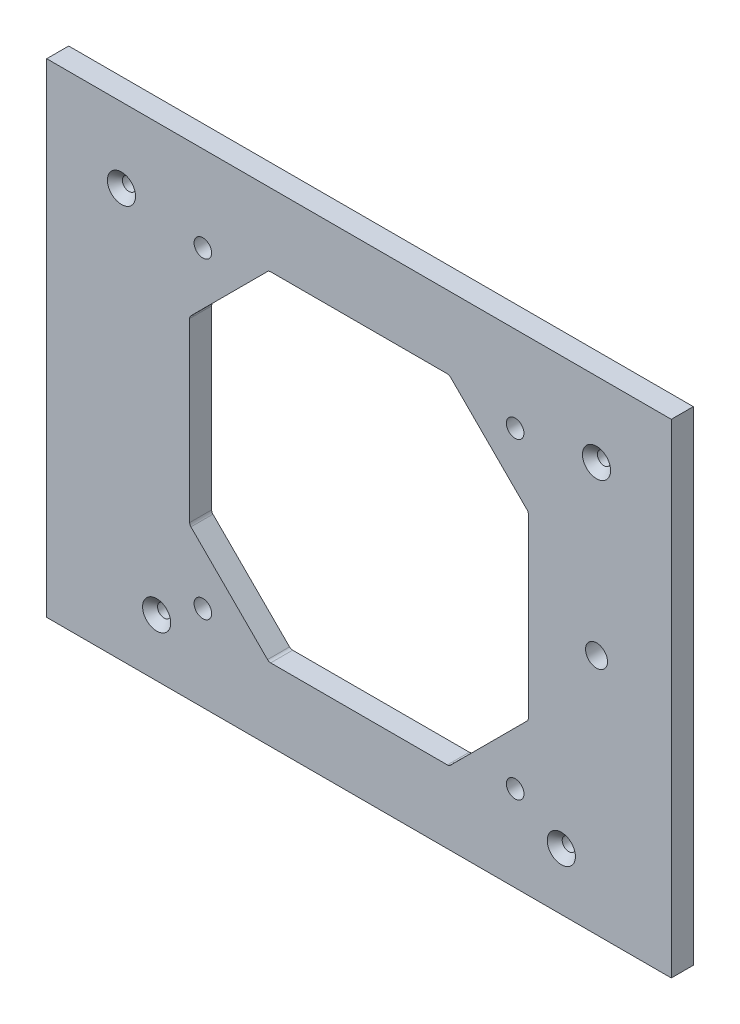
SolidWorks part; units mm, degrees
ref_plane "Front Plane" through (0, 0, 0) normal (0, 0, 1) x (1, 0, 0)
ref_plane "Top Plane" through (0, 0, 0) normal (0, 1, 0) x (1, 0, 0)
ref_plane "Right Plane" through (0, 0, 0) normal (1, 0, 0) x (0, 0, -1)
sketch "Sketch1" plane through (0, 0, 0) normal (0, 0, 1) x (1, 0, 0)
  line L1 (71, -55) -> (-71, -55)
  line L2 (71, -55) -> (71, 55)
  line L3 (71, 55) -> (-71, 55)
  line L4 (-71, -55) -> (-71, 55)
  line L5 (71, -55) -> (-71, 55) construction
  line L6 (71, 55) -> (-71, -55) construction
  point P0 (0, 0)
  dimension "D1" = 142
  dimension "D2" = 110
extrude "Boss-Extrude1" add sketch "Sketch1" along normal mid plane 5
sketch "Sketch3" plane through (0, 0, 2.5) normal (0, 0, 1) x (1, 0, 0)
  line L0 (71, -55) -> (71, 55) construction
  line L1 (71, 55) -> (-71, 55) construction
  line L2 (-71, 55) -> (-71, -55) construction
  circle A0 centre (-54, 38) radius 1.5
  circle A1 centre (54, 38) radius 1.5
  dimension "D3" = 3
  dimension "D1" = 17
  dimension "D2" = 17
  dimension "D4" = 17
extrude "TopCoverHoles" cut sketch "Sketch3" against normal through all
sketch "Sketch5" plane through (0, 0, 2.5) normal (0, 0, 1) x (1, 0, 0)
  line L0 (-71, 55) -> (-71, -55) construction
  line L1 (71, -55) -> (71, 55) construction
  line L2 (-71, -55) -> (71, -55) construction
  circle A0 centre (46, -42) radius 1.5
  circle A1 centre (-46, -42) radius 1.5
  dimension "D3" = 3
  dimension "D1" = 25
  dimension "D2" = 25
  dimension "D4" = 13
extrude "Cut-Extrude1" cut sketch "Sketch5" against normal through all
chamfer "Chamfer1" distance 1.7 angle 45 4 edges at (55.5, 38, 2.5) (-52.5, 38, 2.5) (47.5, -42, 2.5) (-44.5, -42, 2.5)
sketch "Sketch7" plane through (0, 0, 2.5) normal (0, 0, 1) x (1, 0, 0)
  line L0 (-20.5, 38.5) -> (-38.5, 20.5)
  line L1 (20.5, -38.5) -> (-20.5, -38.5)
  line L2 (38.5, -20.5) -> (38.5, 20.5)
  line L3 (20.5, 38.5) -> (-20.5, 38.5)
  line L4 (-38.5, -20.5) -> (-38.5, 20.5)
  line L5 (38.5, -38.5) -> (-38.5, 38.5) construction
  line L6 (38.5, 38.5) -> (-38.5, -38.5) construction
  line L7 (-20.5, -38.5) -> (-38.5, -20.5)
  line L8 (38.5, -20.5) -> (20.5, -38.5)
  line L9 (38.5, 20.5) -> (20.5, 38.5)
  circle A0 centre (0, 0) radius 38.5 construction
  circle A1 centre (-35.5, -35.5) radius 2
  circle A2 centre (35.5, -35.5) radius 2
  circle A3 centre (35.5, 35.5) radius 2
  circle A4 centre (-35.5, 35.5) radius 2
  point P23 (0, 0)
  dimension "D3" = 4
  dimension "D10" = 77
  dimension "D4" = 71
  dimension "D5" = 71
  dimension "D11" = 77
extrude "Fan" cut sketch "Sketch7" against normal through all
chamfer "FanChamfer" [suppressed] distance 3 angle 45
sketch "Sketch8" plane through (0, 0, 2.5) normal (0, 0, 1) x (1, 0, 0)
  line L2 (71, -55) -> (71, 55) construction
  circle A0 centre (54, 0) radius 2.5
  dimension "D1" = 17
  dimension "D2" = 5
extrude "ForLED" cut sketch "Sketch8" against normal through all
fillet "Fillet1" radius 1 8 edges at (38.5, 20.5, 0) (38.5, -20.5, 0) (20.5, -38.5, 0) (-38.5, -20.5, 0) (-38.5, 20.5, 0) (-20.5, 38.5, 0) (20.5, 38.5, 0) (-20.5, -38.5, 0)
